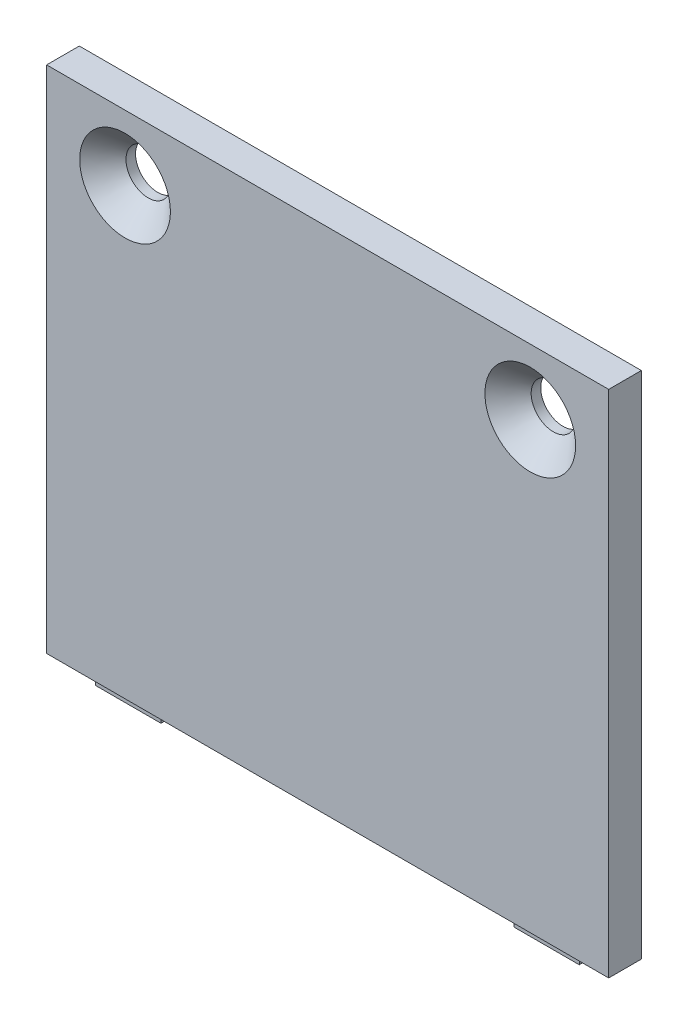
SolidWorks part; units mm, degrees
ref_plane "Alzado" through (0, 0, 0) normal (0, 0, 1) x (1, 0, 0)
ref_plane "Planta" through (0, 0, 0) normal (0, 1, 0) x (1, 0, 0)
ref_plane "Vista lateral" through (0, 0, 0) normal (1, 0, 0) x (0, 0, -1)
sketch "Croquis1" plane through (0, 0, 0) normal (0, 0, 1) x (1, 0, 0)
  line L1 (-21.5, 19.5) -> (21.5, 19.5)
  line L2 (-21.5, 19.5) -> (-21.5, -19.5)
  line L3 (-21.5, -19.5) -> (21.5, -19.5)
  line L4 (21.5, 19.5) -> (21.5, -19.5)
  line L5 (-21.5, 19.5) -> (21.5, -19.5) construction
  line L6 (-21.5, -19.5) -> (21.5, 19.5) construction
  point P0 (0, 0)
  dimension "D1" = 39
  dimension "D2" = 43
extrude "Saliente-Extruir1" add sketch "Croquis1" along normal blind 2.5
sketch "Croquis2" plane through (0, -19.5, 0) normal (0, -1, 0) x (1, 0, 0)
  line L1 (-21.5, 0) -> (21.5, 0) construction
  line L2 (-18.5, 0.75) -> (-13.5, 0.75)
  line L3 (-13.5, 0.75) -> (-13.5, 1.75)
  line L4 (-13.5, 1.75) -> (-18.5, 1.75)
  line L5 (-18.5, 1.75) -> (-18.5, 0.75)
  line L6 (-21.5, 2.5) -> (-21.5, 0) construction
  line L7 (18.5, 0) -> (18.5, 0.75)
  line L8 (18.5, 0.75) -> (13.5, 0.75)
  line L9 (13.5, 0.75) -> (13.5, 1.75)
  line L10 (13.5, 1.75) -> (18.5, 1.75)
  line L11 (18.5, 1.75) -> (18.5, 0.75)
  line L12 (21.5, 2.5) -> (21.5, 0) construction
  point P16 (0, 0)
  point P17 (0, 0)
  dimension "D2" = 1
  dimension "D3" = 5
  dimension "D4" = 5
  dimension "D5" = 3
  dimension "D6" = 0.75
  dimension "D7" = 1
  dimension "D8" = 5
  dimension "D9" = 3
extrude "Saliente-Extruir2" add sketch "Croquis2" along normal blind 1 contours L4 L5 L2 L3 | L11 L10 L9 L8 region at (-16, -19.5, 1.25) region at (16, -19.5, 1.25)
sketch "Croquis3" plane through (0, 0, 2.5) normal (0, 0, 1) x (1, 0, 0)
  line L0 (-21.5, 19.5) -> (-21.5, -19.5) construction
  line L1 (21.5, 19.5) -> (-21.5, 19.5) construction
  line L2 (21.5, -19.5) -> (21.5, 19.5) construction
  point P0 (-15.5, 14.5)
  point P6 (15.5, 14.5)
  dimension "D1" = 6
  dimension "D2" = 5
  dimension "D3" = 6
hole_wizard "Avellanado para tornillo con cabeza avellanada de clavija hexagonal de M31" positions "Croquis3D1" profile "Croquis4" countersink size "M3" standard "DIN"
sketch3d "Croquis3D1"
  point P0 (-15.5, 14.5, 2.5)
  point P3 (15.5, 14.5, 2.5)
sketch "Croquis4" plane through (-15.5, 14.5, 2.5) normal (1, 0, 0) x (0, -1, 0)
  line L0 (0, 0) -> (0, 13.0215)
  line L1 (0, 13.0215) -> (1.7, 12)
  line L2 (1.7, 12) -> (1.7, 1.77)
  line L3 (1.7, 1.77) -> (3.47, 0)
  line L5 (3.47, 0) -> (0, 0)
  line L6 (-1.7, 1.77) -> (-3.47, 0) construction
  line L10 (0, 13.0215) -> (-1.7, 12) construction
  line L11 (0, -6.35) -> (0, 107.95) construction
  dimension "Diámetro de taladro" = 3.4
  dimension "Profundidad de taladro" = 12
  dimension "Ángulo de avellanado cercano" = 6.94
  dimension "Ángulo de avellanado lejano" = 90
  dimension "Ángulo de perforador" = 118
